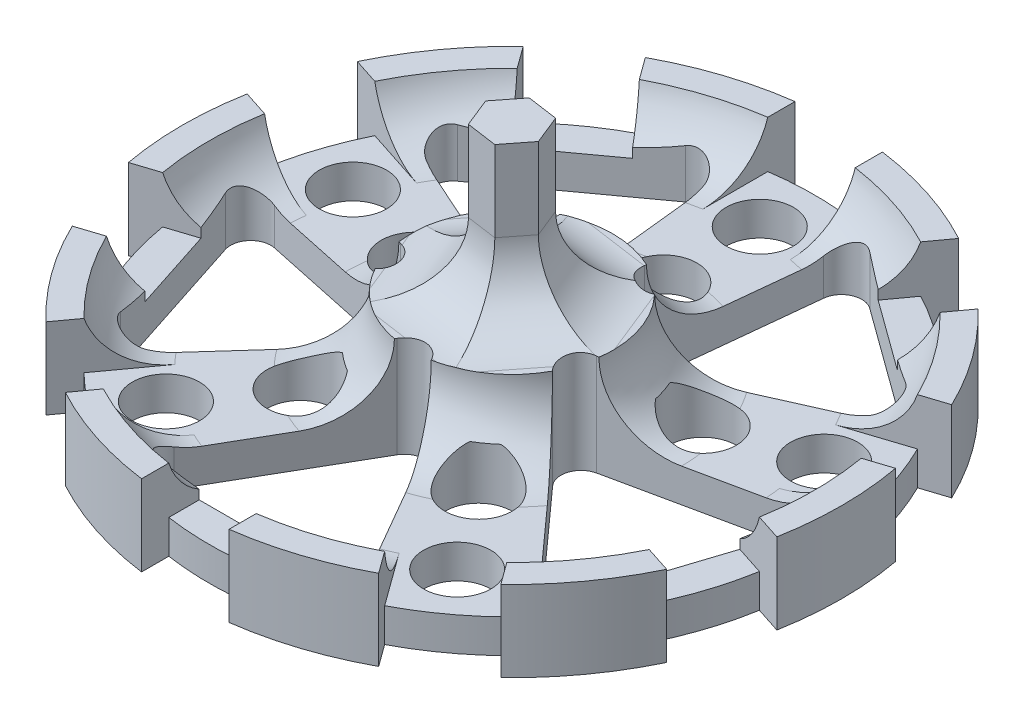
SolidWorks part; units mm, degrees
ref_plane "Front Plane" through (0, 0, 0) normal (0, 0, 1) x (1, 0, 0)
ref_plane "Top Plane" through (0, 0, 0) normal (0, 1, 0) x (1, 0, 0)
ref_plane "Right Plane" through (0, 0, 0) normal (1, 0, 0) x (0, 0, -1)
sketch "Sketch1" plane through (0, 0, 0) normal (0, 1, 0) x (1, 0, 0)
  line L0 (0, 0) -> (0, 49) construction
  line L1 (0, 49) -> (0, -49) construction
  line L2 (0, -49) -> (0, 0) construction
  line L3 (0, 0) -> (-49, 0) construction
  line L4 (-49, 0) -> (49, 0) construction
  line L5 (55.7063, 24.9346) -> (59.7235, 12.5709)
  line L6 (-6.5, -60.6851) -> (6.5, -60.6851)
  line L7 (-6.5, -60.6851) -> (-6.5, 60.6851)
  line L8 (-6.5, 60.6851) -> (6.5, 60.6851)
  line L9 (6.5, -60.6851) -> (6.5, 60.6851)
  line L10 (-6.5, -60.6851) -> (6.5, 60.6851) construction
  line L11 (-6.5, 60.6851) -> (6.5, -60.6851) construction
  line L12 (-59.7235, -12.5709) -> (55.7063, 24.9346)
  line L13 (-55.7063, -24.9346) -> (59.7235, 12.5709)
  line L14 (-59.7235, -12.5709) -> (-55.7063, -24.9346)
  line L15 (40.9284, -45.2747) -> (30.4112, -52.9159)
  line L16 (-30.4112, 52.9159) -> (40.9284, -45.2747)
  line L17 (-40.9284, 45.2747) -> (30.4112, -52.9159)
  line L18 (-30.4112, 52.9159) -> (-40.9284, 45.2747)
  line L19 (-30.4112, -52.9159) -> (-40.9284, -45.2747)
  line L20 (40.9284, 45.2747) -> (-30.4112, -52.9159)
  line L21 (30.4112, 52.9159) -> (-40.9284, -45.2747)
  line L22 (40.9284, 45.2747) -> (30.4112, 52.9159)
  line L23 (-59.7235, 12.5709) -> (-55.7063, 24.9346)
  line L24 (55.7063, -24.9346) -> (-59.7235, 12.5709)
  line L25 (59.7235, -12.5709) -> (-55.7063, 24.9346)
  line L26 (55.7063, -24.9346) -> (59.7235, -12.5709)
  circle A0 centre (0, 0) radius 49
  circle A1 centre (0, 0) radius 45
  point P31 (0, 0)
  dimension "D1" = 98
  dimension "D2" = 90
  dimension "D3" = 13
  dimension "D4" = 5
extrude "Boss-Extrude1" add sketch "Sketch1" along normal blind 12 contours A1 L17 A0 L25 | A1 L24 A0 L12 | A1 L13 A0 L21 | A1 L20 A0 L7 | A1 L9 A0 L17 | A1 L16 A0 L24 | A1 L25 A0 L13 | A1 L12 A0 L20 | A1 L21 A0 L9 | A1 L7 A0 L16
sketch "Sketch2" plane through (0, 0, 0) normal (0, -1, 0) x (-1, 0, 0)
  circle A1 centre (0, 0) radius 45
extrude "Boss-Extrude2" add sketch "Sketch2" against normal blind 5
fillet "Fillet1" radius 10 10 edges at (-36.4058, 5, -26.4503) (-45, 5, 0) (-36.4058, 5, 26.4503) (-13.9058, 5, 42.7975) (13.9058, 5, 42.7975) (36.4058, 5, 26.4503) (45, 5, 0) (36.4058, 5, -26.4503) (13.9058, 5, -42.7975) (-13.9058, 5, -42.7975)
sketch "Sketch3" plane through (0, 5, 0) normal (0, 1, 0) x (1, 0, 0)
  circle A0 centre (0, 0) radius 15
  dimension "D1" = 30
extrude "Boss-Extrude3" add sketch "Sketch3" along normal blind 10
sketch "Sketch4" plane through (0, 15, 0) normal (0, 1, 0) x (1, 0, 0)
  line L1 (1.7244, -4.2849) -> (4.573, -0.6491)
  line L2 (4.573, -0.6491) -> (2.8486, 3.6358)
  line L3 (2.8486, 3.6358) -> (-1.7244, 4.2849)
  line L4 (-1.7244, 4.2849) -> (-4.573, 0.6491)
  line L5 (-4.573, 0.6491) -> (-2.8486, -3.6358)
  line L6 (-2.8486, -3.6358) -> (1.7244, -4.2849)
  circle A0 centre (0, 0) radius 4 construction
  dimension "D1" = 8
extrude "Boss-Extrude4" add sketch "Sketch4" along normal blind 22
fillet "Fillet3" radius 10 6 edges at (-0.5621, 15, 3.9603) (3.1487, 15, 2.467) (3.7108, 15, -1.4933) (0.5621, 15, -3.9603) (-3.1487, 15, -2.467) (-3.7108, 15, 1.4933)
fillet "Fillet7" radius 10 1 edges at (0, 5, -15)
sketch "Sketch5" plane through (0, 0, 0) normal (0, -1, 0) x (-1, 0, 0)
  line L0 (0, 0) -> (0, -54.4624) construction
  line L1 (0, -54.4624) -> (0, 52.6767) construction
  line L2 (0, 52.6767) -> (0, 0) construction
  line L3 (0, 0) -> (59.4759, 0) construction
  line L4 (59.4759, 0) -> (-60.0254, 0) construction
  line L5 (-9.5106, -3.0902) -> (-43.3946, 4.1121)
  line L6 (0, -10) -> (-17.3205, -40)
  line L7 (-17.3205, -40) -> (17.3205, -40)
  line L8 (17.3205, -40) -> (0, -10)
  line L9 (-43.3946, 4.1121) -> (-32.6899, -28.8335)
  line L10 (-32.6899, -28.8335) -> (-9.5106, -3.0902)
  line L11 (-5.8779, 8.0902) -> (-9.4988, 42.5414)
  line L12 (-9.4988, 42.5414) -> (-37.524, 22.1799)
  line L13 (-37.524, 22.1799) -> (-5.8779, 8.0902)
  line L14 (5.8779, 8.0902) -> (37.524, 22.1799)
  line L15 (37.524, 22.1799) -> (9.4988, 42.5414)
  line L16 (9.4988, 42.5414) -> (5.8779, 8.0902)
  line L17 (9.5106, -3.0902) -> (32.6899, -28.8335)
  line L18 (32.6899, -28.8335) -> (43.3946, 4.1121)
  line L19 (43.3946, 4.1121) -> (9.5106, -3.0902)
  circle A0 centre (0, 0) radius 30
  circle A1 centre (0, -30) radius 10 construction
  point P26 (0, 0)
  dimension "D1" = 60
  dimension "D2" = 5
extrude "Cut-Extrude1" cut sketch "Sketch5" against normal blind 18 contours A0 L17 L18 L19 | L17 A0 L19 | A0 L6 L7 L8 | L6 A0 L8 | A0 L5 L9 L10 | L5 A0 L10 | L11 A0 L13 | A0 L11 L12 L13 | L14 A0 L16 | A0 L14 L15 L16
fillet "Fillet8" radius 3 10 edges at (37.524, 4.5876, -22.1799) (9.4988, 4.5876, -42.5414) (-9.4988, 4.5876, -42.5414) (-37.524, 4.5876, -22.1799) (-43.3946, 4.5876, -4.1121) (-32.6899, 4.5876, 28.8335) (-17.3205, 4.5876, 40) (17.3205, 4.5876, 40) (32.6899, 4.5876, 28.8335) (43.3946, 4.5876, -4.1121)
sketch "Sketch6" plane through (0, 0, 0) normal (0, -1, 0) x (-1, 0, 0)
  circle A0 centre (0, 0) radius 6
  dimension "D1" = 12
extrude "Cut-Extrude2" cut sketch "Sketch6" against normal blind 8
fillet "Fillet9" radius 4 1 edges at (0, 0, -6)
sketch "Sketch7" plane through (0, 0, 0) normal (0, -1, 0) x (-1, 0, 0)
  line L0 (-18.5008, -22.589) -> (0, 0) construction
  line L1 (0, 0) -> (-42.7975, 13.9058) construction
  arc A0 (-40.3401, 19.9418) -> (-44.3573, 7.5781) centre (0, 0) ccw construction
  circle A1 centre (-35.0311, 11.3823) radius 5
  circle A2 centre (-21.3988, 6.9529) radius 5
  dimension "D1" = 10
  dimension "D2" = 10
extrude "Cut-Extrude3" cut sketch "Sketch7" against normal blind 8
pattern_circular "CirPattern1" count 5 over 360 about axis through (0, 0, 0) along (0, 1, 0) of "Cut-Extrude3"
fillet "Fillet10" radius 3 5 edges at (-5.8779, 8.006, -8.0902) (-9.5106, 7.9226, 3.0902) (0, 7.9394, 10) (9.5106, 8.0624, 3.0902) (5.8779, 8.2183, -8.0902)
